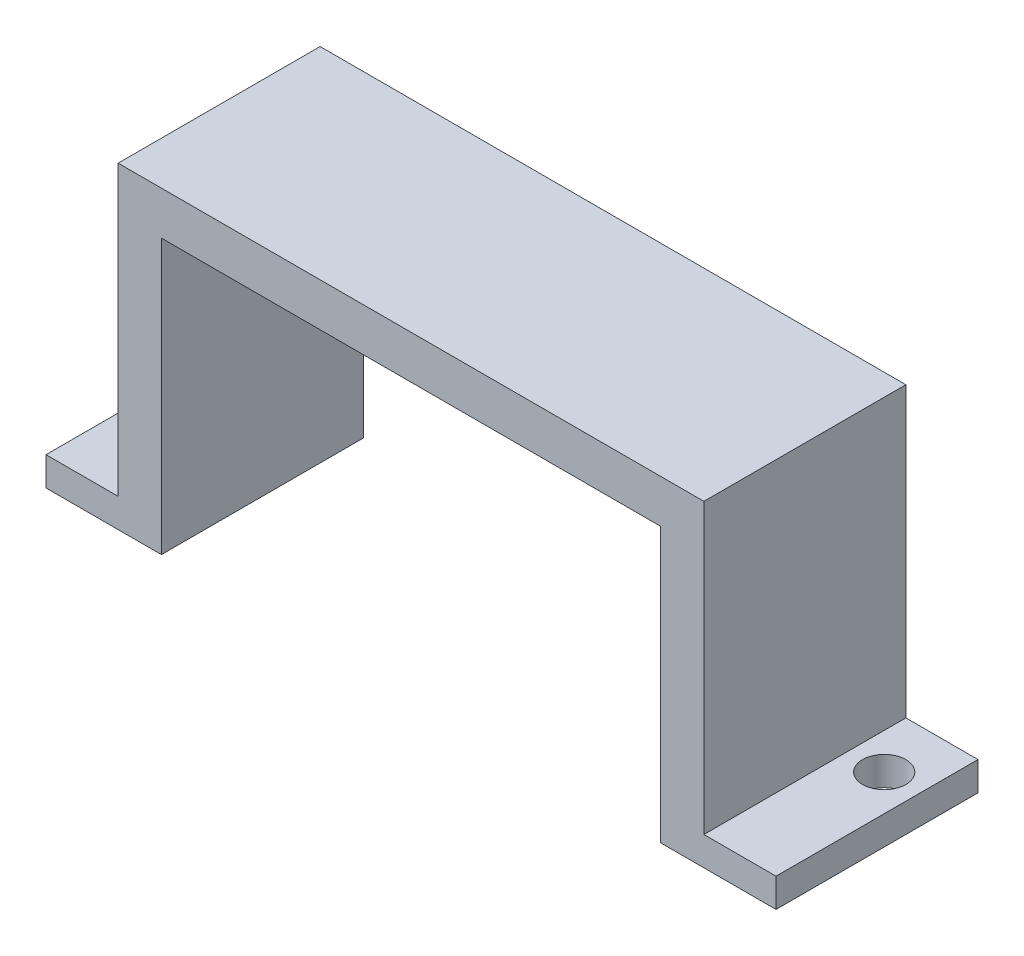
SolidWorks part; units mm, degrees
ref_plane "Front Plane" through (0, 0, 0) normal (0, 0, 1) x (1, 0, 0)
ref_plane "Top Plane" through (0, 0, 0) normal (0, 1, 0) x (1, 0, 0)
ref_plane "Right Plane" through (0, 0, 0) normal (1, 0, 0) x (0, 0, -1)
sketch "Sketch2" plane through (0, 0, 0) normal (0, 0, 1) x (1, 0, 0)
  line L1 (-25.67, -3.38) -> (8.93, -3.38)
  line L2 (-25.67, -3.38) -> (-25.67, 15.62)
  line L3 (-25.67, 15.62) -> (8.93, 15.62)
  line L4 (8.93, -3.38) -> (8.93, 15.62)
  line L5 (11.93, -1.38) -> (11.93, 18.62)
  line L6 (-28.67, 18.62) -> (11.93, 18.62)
  line L7 (-28.67, -1.38) -> (-28.67, 18.62)
  line L8 (-25.67, -3.38) -> (-12.23, -3.38)
  line L9 (8.93, -3.38) -> (11.93, -3.38)
  line L10 (-28.67, -6.38) -> (-28.67, 18.62) construction
  line L11 (-28.67, -6.38) -> (11.93, -6.38) construction
  line L12 (11.93, -6.38) -> (11.93, 18.62) construction
  line L14 (-12.23, -3.38) -> (-33.67, -3.38)
  line L16 (-28.67, -1.38) -> (-33.67, -1.38)
  line L17 (-33.67, -3.38) -> (-33.67, -1.38)
  line L18 (11.93, -3.38) -> (16.93, -3.38)
  line L20 (11.93, -1.38) -> (16.93, -1.38)
  line L21 (16.93, -3.38) -> (16.93, -1.38)
  point P0 (0, 0)
  dimension "D1" = 34.6
  dimension "D2" = 19
  dimension "D4" = 2
  dimension "D5" = 5
  dimension "D6" = 2
  dimension "D7" = 5
  dimension "D3" = 3
extrude "Boss-Extrude1" add sketch "Sketch2" along normal blind 14 contours L18 L21 L20 L5 L6 L7 L16 L17 L14 L8 L2 L3 L4 L9 region at (-29.67, -2.8282, 0)
sketch "Sketch3" plane through (0, -1.38, 0) normal (0, 1, 0) x (1, 0, 0)
  line L0 (11.93, 0) -> (16.93, 0) construction
  line L1 (11.93, -14) -> (11.93, 0) construction
  line L2 (-28.67, 0) -> (-33.67, 0) construction
  line L3 (-28.67, -14) -> (-28.67, 0) construction
  circle A0 centre (14.43, -4) radius 1.9118
  circle A1 centre (-31.17, -4) radius 1.7839
  dimension "D1" = 4
  dimension "D2" = 2.5
  dimension "D3" = 4
  dimension "D4" = 2.5
hole_wizard "Ø3.0 (3) Diameter Hole1" positions "Sketch4" profile "Sketch6" hole size "Ø3.0" standard "ANSI Metric" end condition through all
sketch "Sketch4" plane through (0, -1.38, 0) normal (0, 1, 0) x (1, 0, 0)
  point P0 (14.43, -4)
  point P4 (-31.17, -4)
sketch "Sketch6" plane through (14.43, -1.38, 4) normal (1, 0, 0) x (0, 0, 1)
  line L0 (0, 0) -> (0, 2)
  line L1 (0, 2) -> (1.5, 2)
  line L2 (1.5, 2) -> (1.5, 0)
  line L5 (1.5, 0) -> (0, 0)
  line L11 (0, -6.35) -> (0, 107.95) construction
  dimension "Thru Hole Dia." = 3
  dimension "Thru Hole Depth" = 2
